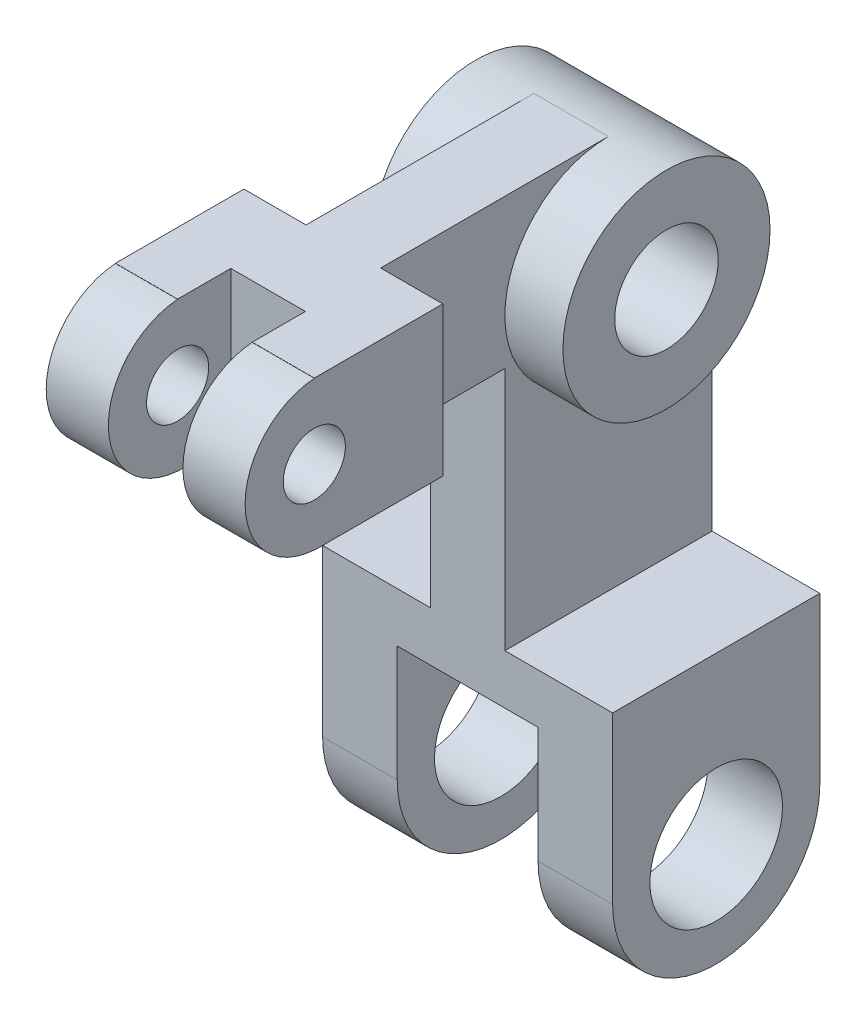
SolidWorks part; units mm, degrees
ref_plane "Plano frontal" through (0, 0, 0) normal (0, 0, 1) x (1, 0, 0)
ref_plane "Plano superior" through (0, 0, 0) normal (0, 1, 0) x (1, 0, 0)
ref_plane "Plano direito" through (0, 0, 0) normal (1, 0, 0) x (0, 0, -1)
sketch "Esboço1" plane through (0, 0, 0) normal (1, 0, 0) x (0, 0, -1)
  line L0 (-62.2573, 0) -> (55.5718, 0) construction
  line L1 (0, 169.4232) -> (0, -61.0604) construction
  line L2 (-84.7113, 135) -> (0, 135)
  line L3 (25, 110) -> (25, 0)
  line L4 (-25, 0) -> (-25, 99)
  line L6 (-84.7113, 99) -> (-25, 99)
  line L7 (-25, 40) -> (25, 40)
  line L8 (0, 135) -> (-137.6336, 135) construction
  line L9 (-17.3494, 128) -> (35.0817, 128) construction
  arc A0 (-25, 0) -> (25, 0) centre (0, 0) ccw
  circle A1 centre (0, 0) radius 16
  circle A2 centre (0, 110) radius 25
  circle A3 centre (0, 110) radius 12.5
  circle A4 centre (-84.7113, 117) radius 18
  circle A5 centre (-84.7113, 117) radius 7.5
  dimension "D1" = 50
  dimension "D2" = 32
  dimension "D3" = 50
  dimension "D4" = 25
  dimension "D5" = 36
  dimension "D6" = 15
  dimension "D7" = 110
  dimension "D8" = 85
  dimension "D9" = 40
extrude "Ressalto-extrusão1" add sketch "Esboço1" along normal mid plane 48 contours A4 A5 region at (0, 129.3679, 72.3434)
extrude "Ressalto-extrusão2" add sketch "Esboço1<3>" along normal mid plane 18 contours A4 L6 L4 L7 L3 A2 region at (0, 87.1737, 18.937)
sketch "Esboço1<3>" plane through (0, 0, 0) normal (1, 0, 0) x (0, 0, -1) same geometry as "Esboço1"
extrude "Ressalto-extrusão3" add sketch "Esboço1<4>" along normal mid plane 46 contours A2 A3 region at (0, 127.1777, -17.1777)
sketch "Esboço1<4>" plane through (0, 0, 0) normal (1, 0, 0) x (0, 0, -1) same geometry as "Esboço1"
extrude "Ressalto-extrusão4" add sketch "Esboço1<5>" along normal mid plane 70 contours A0 L3 L7 L4 region at (0, 20, -24.1799)
sketch "Esboço1<5>" plane through (0, 0, 0) normal (1, 0, 0) x (0, 0, -1) same geometry as "Esboço1"
sketch "Esboço2" plane through (0, 0, 0) normal (0, 0, 1) x (1, 0, 0)
  line L6 (-35, 0) -> (-35, 40) construction
  line L7 (-17, 28) -> (17, 28)
  line L8 (-17, 28) -> (-17, -38.3099)
  line L9 (-17, -38.3099) -> (17, -38.3099)
  line L10 (17, 28) -> (17, -38.3099)
  line L11 (35, 40) -> (9, 40) construction
  dimension "D1" = 18
  dimension "D2" = 34
  dimension "D3" = 12
extrude "Corte-extrusão1" cut sketch "Esboço2" against normal mid plane 140
ref_plane "Plano1" through (0, 0, 55) normal (0, 0, 1) x (1, 0, 0)
sketch "Esboço3" plane through (0, 0, 55) normal (0, 0, 1) x (1, 0, 0)
  line L1 (-24, 135) -> (24, 135)
  line L2 (-24, 135) -> (-24, 99)
  line L3 (-24, 99) -> (24, 99)
  line L4 (24, 135) -> (24, 99)
extrude "Ressalto-extrusão7" add sketch "Esboço3" along normal blind 31
sketch "Esboço4" plane through (0, 0, 0) normal (1, 0, 0) x (0, 0, -1)
  line L0 (-86, 109.6116) -> (-86, 124.3884) construction
  circle A0 centre (-86, 117) radius 7.5
  dimension "D1" = 15
extrude "Corte-extrusão2" cut sketch "Esboço4" against normal mid plane 97
sketch "Esboço5" plane through (0, 0, 0) normal (0, 1, 0) x (1, 0, 0)
  line L0 (-24, -86) -> (-24, -102.7113) construction
  line L1 (-9, -109.4488) -> (9, -109.4488)
  line L2 (-9, -109.4488) -> (-9, -73.1613)
  line L3 (-9, -73.1613) -> (9, -73.1613)
  line L4 (9, -109.4488) -> (9, -73.1613)
  dimension "D1" = 18
  dimension "D2" = 15
extrude "Corte-extrusão3" cut sketch "Esboço5" along normal blind 189
